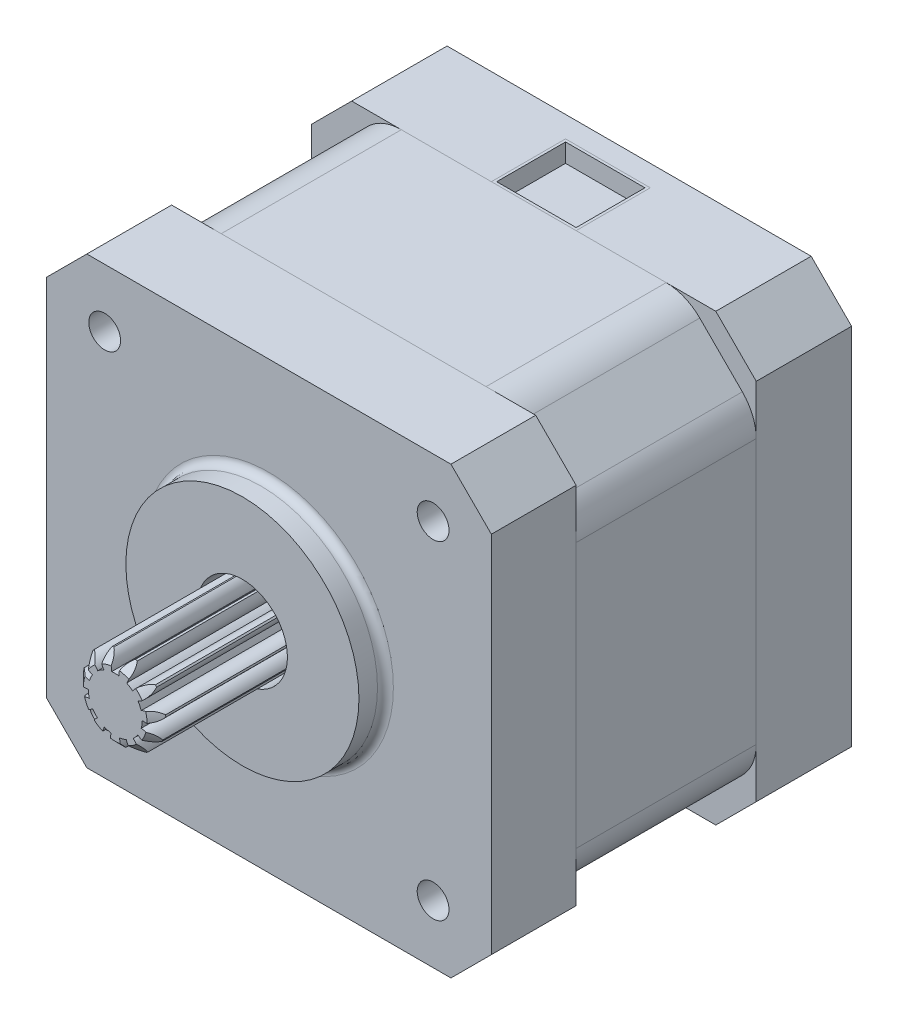
SolidWorks part; units mm, degrees
other "KABLO"
other "ÖN"
other "ORTA"
other "ARKA"
other "ŞAFT"
ref_plane "Front Plane" through (0, 0, 0) normal (0, 0, 1) x (1, 0, 0)
ref_plane "Top Plane" through (0, 0, 0) normal (0, 1, 0) x (1, 0, 0)
ref_plane "Right Plane" through (0, 0, 0) normal (1, 0, 0) x (0, 0, -1)
sketch "Sketch1" plane through (0, 0, 0) normal (0, 0, 1) x (1, 0, 0)
  line L0 (-15.5, 15.5) -> (15.5, 15.5) construction
  line L1 (17.1838, 21) -> (-17.1838, 21)
  line L2 (21, 17.1838) -> (21, -17.1838)
  line L3 (17.1838, -21) -> (-17.1838, -21)
  line L4 (-21, 17.1838) -> (-21, -17.1838)
  line L5 (19.0919, 19.0919) -> (-19.0919, -19.0919) construction
  line L6 (19.0919, -19.0919) -> (-19.0919, 19.0919) construction
  line L7 (15.5, 15.5) -> (15.5, -15.5) construction
  line L8 (15.5, -15.5) -> (-15.5, -15.5) construction
  line L9 (-15.5, -15.5) -> (-15.5, 15.5) construction
  line L10 (17.1838, 21) -> (21, 17.1838)
  line L11 (21, 17.1838) -> (21, 21) construction
  line L12 (21, 21) -> (17.1838, 21) construction
  line L13 (19.0919, 19.0919) -> (21, 21) construction
  line L14 (19.0919, 19.0919) -> (-19.0919, 19.0919) construction
  line L15 (-19.0919, 19.0919) -> (-19.0919, -19.0919) construction
  line L16 (-19.0919, -19.0919) -> (19.0919, -19.0919) construction
  line L17 (19.0919, -19.0919) -> (19.0919, 19.0919) construction
  line L18 (21, -17.1838) -> (17.1838, -21)
  line L19 (-17.1838, -21) -> (-21, -17.1838)
  line L20 (-21, 17.1838) -> (-17.1838, 21)
  line L21 (-19.0919, -19.0919) -> (-21, -21) construction
  line L22 (19.0919, -19.0919) -> (21, -21) construction
  line L23 (-19.0919, 19.0919) -> (-21, 21) construction
  line L24 (21, -17.1838) -> (21, -21) construction
  line L25 (21, -21) -> (17.1838, -21) construction
  line L26 (-17.1838, -21) -> (-21, -21) construction
  line L27 (-21, -21) -> (-21, -17.1838) construction
  line L28 (-21, 17.1838) -> (-21, 21) construction
  line L29 (-21, 21) -> (-17.1838, 21) construction
  circle A0 centre (-15.5, 15.5) radius 1.5 construction
  circle A1 centre (15.5, 15.5) radius 1.5 construction
  circle A2 centre (-15.5, -15.5) radius 1.5 construction
  circle A3 centre (15.5, -15.5) radius 1.5 construction
  point P0 (0, 0)
  dimension "D2" = 3
  dimension "D1" = 42
  dimension "D3" = 31
  dimension "D4" = 54
extrude "Boss-Extrude1" add sketch "Sketch1" against normal blind 8
sketch "Sketch3" plane through (0, 0, -8) normal (0, 0, -1) x (-1, 0, 0)
  line L0 (-19.6881, 15.6673) -> (-15.6673, 19.6881)
  line L1 (15.6673, 19.6881) -> (19.6881, 15.6673)
  line L2 (19.6881, -15.6673) -> (15.6673, -19.6881)
  line L3 (-15.6673, -19.6881) -> (-19.6881, -15.6673)
  line L4 (0, 0) -> (-17.6777, -17.6777) construction
  line L5 (0, 0) -> (17.6777, 17.6777) construction
  line L6 (-17.6777, 17.6777) -> (0, 0) construction
  line L7 (0, 0) -> (17.6777, -17.6777) construction
  line L8 (-17.1838, 21) -> (-21, 17.1838)
  line L9 (-21, 17.1838) -> (-21, -17.1838)
  line L10 (-21, -17.1838) -> (-17.1838, -21)
  line L11 (-17.1838, -21) -> (17.1838, -21)
  line L12 (17.1838, -21) -> (21, -17.1838)
  line L13 (21, -17.1838) -> (21, 17.1838)
  line L14 (21, 17.1838) -> (17.1838, 21)
  line L15 (17.1838, 21) -> (-17.1838, 21)
  line L16 (-17.6777, -17.6777) -> (-19.0919, -19.0919) construction
  line L17 (-21, 12.5) -> (-21, -12.5)
  line L18 (-17.1838, -21) -> (-21, -17.1838) construction
  line L19 (-12.5, -21) -> (12.5, -21)
  line L21 (21, -12.5) -> (21, 12.5)
  line L23 (12.5, 21) -> (-12.5, 21)
  arc A0 (-19.6881, -15.6673) -> (-21, -12.5) centre (-16.5208, -12.5) cw
  arc A1 (-15.6673, -19.6881) -> (-12.5, -21) centre (-12.5, -16.5208) ccw
  arc A2 (15.6673, -19.6881) -> (12.5, -21) centre (12.5, -16.5208) cw
  arc A3 (19.6881, -15.6673) -> (21, -12.5) centre (16.5208, -12.5) ccw
  arc A4 (19.6881, 15.6673) -> (21, 12.5) centre (16.5208, 12.5) cw
  arc A5 (15.6673, 19.6881) -> (12.5, 21) centre (12.5, 16.5208) ccw
  arc A6 (-15.6673, 19.6881) -> (-12.5, 21) centre (-12.5, 16.5208) cw
  arc A7 (-19.6881, 15.6673) -> (-21, 12.5) centre (-16.5208, 12.5) ccw
  dimension "D3" = 25
  dimension "D2" = 50
  dimension "D1" = 0
extrude "Boss-Extrude2" add sketch "Sketch3" along normal blind 17 separate body
sketch "Sketch4" plane through (0, 0, -25) normal (0, 0, -1) x (-1, 0, 0)
  line L8 (-17.1838, 21) -> (-21, 17.1838)
  line L9 (-21, 17.1838) -> (-21, -17.1838)
  line L10 (-21, -17.1838) -> (-17.1838, -21)
  line L11 (-17.1838, -21) -> (17.1838, -21)
  line L12 (17.1838, -21) -> (21, -17.1838)
  line L13 (21, -17.1838) -> (21, 17.1838)
  line L14 (21, 17.1838) -> (17.1838, 21)
  line L15 (17.1838, 21) -> (-17.1838, 21)
  line L16 (-17.1838, 21) -> (-21, 17.1838)
  line L17 (-21, 17.1838) -> (-21, -17.1838)
  line L18 (-21, -17.1838) -> (-17.1838, -21)
  line L19 (-17.1838, -21) -> (17.1838, -21)
  line L20 (17.1838, -21) -> (21, -17.1838)
  line L21 (21, -17.1838) -> (21, 17.1838)
  line L22 (21, 17.1838) -> (17.1838, 21)
  line L23 (17.1838, 21) -> (-17.1838, 21)
  dimension "D1" = 0
extrude "Boss-Extrude3" add sketch "Sketch4" along normal blind 9 separate body
sketch "Sketch5" plane through (0, 0, 0) normal (0, 0, 1) x (1, 0, 0)
  circle A0 centre (-15.5, 15.5) radius 1.5 construction
  circle A1 centre (15.5, 15.5) radius 1.5 construction
  circle A2 centre (15.5, -15.5) radius 1.5 construction
  circle A3 centre (-15.5, -15.5) radius 1.5 construction
  circle A4 centre (-15.5, 15.5) radius 1.5
  circle A5 centre (15.5, 15.5) radius 1.5
  circle A6 centre (15.5, -15.5) radius 1.5
  circle A7 centre (-15.5, -15.5) radius 1.5
extrude "Cut-Extrude1" cut sketch "Sketch5" against normal blind 4.5
sketch "Sketch6" plane through (0, 0, 0) normal (0, 0, 1) x (1, 0, 0)
  circle A0 centre (0, 0) radius 11
  dimension "D1" = 22
extrude "Boss-Extrude4" add sketch "Sketch6" along normal blind 2.5
sketch "Sketch9" plane through (0, 0, 2.5) normal (0, 0, 1) x (1, 0, 0)
  circle A0 centre (0, 0) radius 4.25
  dimension "D1" = 8.5
extrude "Cut-Extrude2" cut sketch "Sketch9" against normal blind 3
sketch "Sketch8" plane through (0, 0, -0.5) normal (0, 0, 1) x (1, 0, 0)
  circle A0 centre (0, 0) radius 3.9
  dimension "D1" = 7.8
extrude "Boss-Extrude5" add sketch "Sketch8" along normal blind 15 separate body
sketch "Sketch11" plane through (0, 0, -0.5) normal (0, 0, 1) x (1, 0, 0)
  circle A2 centre (0, 0) radius 4
  circle A3 centre (0, 0) radius 4.25 construction
  circle A4 centre (0, 0) radius 4.25 construction
  circle A5 centre (0, 0) radius 2.75
  dimension "D2" = 5.5
  dimension "D1" = 0.25
extrude "Boss-Extrude6" add sketch "Sketch11" along normal blind 0.5
fillet "Fillet1" radius 0.75 1 edges at (-11, 0, 0)
sketch "Sketch12" plane through (0, 0, 0) normal (1, 0, 0) x (0, 0, -1)
  line L0 (-14.5, 3) -> (-13.6, 3.9)
  line L1 (-14.5, 3.9) -> (-14.5, -3.9) construction
  line L2 (0.5, 3.9) -> (-14.5, 3.9) construction
  line L3 (-13.6, 3.9) -> (-13.6, 3) construction
  line L4 (-13.6, 3) -> (-14.5, 3) construction
  line L5 (-14.5, 3) -> (-14.5, 3.9)
  line L6 (-14.5, 3.9) -> (-13.6, 3.9)
  line L7 (-14.5, 0) -> (0, 0) construction
  dimension "D1" = 6
revolve "Cut-Revolve1" cut sketch "Sketch12" angle 360 about L7
sketch "Sketch13" plane through (0, 21, 0) normal (0, 1, 0) x (1, 0, 0)
  line L0 (0, 32) -> (0, 25) construction
  line L2 (-12.5, 25) -> (12.5, 25) construction
  line L3 (0, 32) -> (0, 34) construction
  line L4 (-4, 25) -> (4, 25)
  line L5 (-4, 25) -> (-4, 32)
  line L6 (-4, 32) -> (4, 32)
  line L7 (4, 25) -> (4, 32)
  line L8 (-17.1838, 34) -> (17.1838, 34) construction
  dimension "D1" = 2
  dimension "D2" = 8
extrude "Cut-Extrude3" cut sketch "Sketch13" against normal blind 2
sketch "Sketch14" plane through (0, 19, 0) normal (0, 1, 0) x (1, 0, 0)
  line L4 (-4, 32) -> (-4, 25)
  line L5 (-4, 25) -> (4, 25)
  line L6 (4, 25) -> (4, 32)
  line L7 (4, 32) -> (-4, 32)
  line L8 (-4, 32) -> (-4, 25)
  line L9 (-4, 25) -> (4, 25)
  line L10 (4, 25) -> (4, 32)
  line L11 (4, 32) -> (-4, 32)
  dimension "D1" = 0
extrude "Boss-Extrude7" add sketch "Sketch14" along normal blind 0.25 separate body
sketch "Sketch15" plane through (0, 19.25, 0) normal (0, 1, 0) x (1, 0, 0)
  line L0 (3.75, 25.25) -> (3.75, 31.75)
  line L1 (3.75, 31.75) -> (-3.75, 31.75)
  line L2 (-3.75, 31.75) -> (-3.75, 25.25)
  line L3 (-3.75, 25.25) -> (3.75, 25.25)
  line L4 (4, 32) -> (-4, 32)
  line L5 (-4, 32) -> (-4, 25)
  line L6 (-4, 25) -> (4, 25)
  line L7 (4, 25) -> (4, 32)
  line L8 (4, 32) -> (-4, 32)
  line L9 (-4, 32) -> (-4, 25)
  line L10 (-4, 25) -> (4, 25)
  line L11 (4, 25) -> (4, 32)
  dimension "D1" = 0
  dimension "D2" = 0.25
extrude "Boss-Extrude8" add sketch "Sketch15" along normal up to surface (1.75 mm away) up to face at (0, 21, -29)
sketch "Szkic1" plane through (0, 0, 14.5) normal (0, 0, 1) x (1, 0, 0)
  circle A0 centre (0, 0) radius 3.9 construction
  arc A1 (2.1351, -1.3924) -> (3.5094, -1.7012) centre (3.067, -0.4575) ccw
  arc A2 (3.5839, -1.5382) -> (3.872, 0.4662) centre (0, 0) ccw
  arc A3 (3.5839, -1.5382) -> (2.4505, -0.7018) centre (2.3543, -2.0183) ccw
  arc A4 (2.4505, -0.7018) -> (2.5489, -0.017) centre (0, 0) ccw
  arc A5 (2.5489, -0.017) -> (3.872, 0.4662) centre (2.8275, 1.2733) ccw
  arc A6 (3.8465, 0.6436) -> (3.0053, 2.4856) centre (0, 0) ccw
  arc A7 (3.8465, 0.6436) -> (2.4409, 0.7344) centre (3.0717, -0.4251) ccw
  arc A8 (2.4409, 0.7344) -> (2.1535, 1.3638) centre (0, 0) ccw
  arc A9 (2.1535, 1.3638) -> (3.0053, 2.4856) centre (1.6903, 2.5998) ccw
  arc A10 (2.888, 2.621) -> (1.1845, 3.7158) centre (0, 0) ccw
  arc A11 (2.888, 2.621) -> (1.6564, 1.9375) centre (2.8139, 1.3031) ccw
  arc A12 (1.6564, 1.9375) -> (1.0743, 2.3115) centre (0, 0) ccw
  arc A13 (1.0743, 2.3115) -> (1.1845, 3.7158) centre (0.0164, 3.1009) ccw
  arc A14 (2.1833, -3.2316) -> (3.5094, -1.7012) centre (0, 0) ccw
  arc A15 (1.0125, 3.7663) -> (0.3459, 2.5254) centre (1.6627, 2.6175) ccw
  arc A16 (0.3459, 2.5254) -> (-0.3459, 2.5254) centre (0, 0) ccw
  arc A17 (-0.3459, 2.5254) -> (-1.0125, 3.7663) centre (-1.6627, 2.6175) ccw
  arc A18 (-1.1845, 3.7158) -> (-2.888, 2.621) centre (0, 0) ccw
  arc A19 (-1.1845, 3.7158) -> (-1.0743, 2.3115) centre (-0.0164, 3.1009) ccw
  arc A20 (-1.0743, 2.3115) -> (-1.6564, 1.9375) centre (0, 0) ccw
  arc A21 (-1.6564, 1.9375) -> (-2.888, 2.621) centre (-2.8139, 1.3031) ccw
  arc A22 (-3.0053, 2.4856) -> (-3.8465, 0.6436) centre (0, 0) ccw
  arc A23 (-3.0053, 2.4856) -> (-2.1535, 1.3638) centre (-1.6903, 2.5998) ccw
  arc A24 (-2.1535, 1.3638) -> (-2.4409, 0.7344) centre (0, 0) ccw
  arc A25 (-2.4409, 0.7344) -> (-3.8465, 0.6436) centre (-3.0717, -0.4251) ccw
  arc A26 (-3.872, 0.4662) -> (-3.5839, -1.5382) centre (0, 0) ccw
  arc A27 (-3.872, 0.4662) -> (-2.5489, -0.017) centre (-2.8275, 1.2733) ccw
  arc A28 (-2.5489, -0.017) -> (-2.4505, -0.7018) centre (0, 0) ccw
  arc A29 (-2.4505, -0.7018) -> (-3.5839, -1.5382) centre (-2.3543, -2.0183) ccw
  arc A30 (-3.5094, -1.7012) -> (-2.1833, -3.2316) centre (0, 0) ccw
  arc A31 (-3.5094, -1.7012) -> (-2.1351, -1.3924) centre (-3.067, -0.4575) ccw
  arc A32 (-2.1351, -1.3924) -> (-1.6821, -1.9152) centre (0, 0) ccw
  arc A33 (-1.6821, -1.9152) -> (-2.1833, -3.2316) centre (-0.8894, -2.9707) ccw
  arc A34 (-2.0326, -3.3285) -> (-0.0896, -3.899) centre (0, 0) ccw
  arc A35 (-2.0326, -3.3285) -> (-1.0434, -2.3257) centre (-2.3328, -2.0431) ccw
  arc A36 (-1.0434, -2.3257) -> (-0.3796, -2.5206) centre (0, 0) ccw
  arc A37 (-0.3796, -2.5206) -> (-0.0896, -3.899) centre (0.8579, -2.98) ccw
  arc A38 (0.0896, -3.899) -> (2.0326, -3.3285) centre (0, 0) ccw
  arc A39 (0.0896, -3.899) -> (0.3796, -2.5206) centre (-0.8579, -2.98) ccw
  arc A40 (0.3796, -2.5206) -> (1.0434, -2.3257) centre (0, 0) ccw
  arc A41 (1.0434, -2.3257) -> (2.0326, -3.3285) centre (2.3328, -2.0431) ccw
  arc A43 (2.1833, -3.2316) -> (1.6821, -1.9152) centre (0.8894, -2.9707) ccw
  arc A44 (1.6821, -1.9152) -> (2.1351, -1.3924) centre (0, 0) ccw
  arc A45 (1.0125, 3.7663) -> (-1.0125, 3.7663) centre (0, 0) ccw
extrude "Wytnij-wyciągnięcie1" cut sketch "Szkic1" against normal blind 15
sketch "Szkic2" plane through (0, 0, -34) normal (0, 0, -1) x (-1, 0, 0)
  circle A0 centre (0, 0) radius 4.25 construction
  circle A1 centre (0, 0) radius 11 construction
  circle A2 centre (0, 0) radius 4.25
  circle A3 centre (0, 0) radius 11
extrude "Wytnij-wyciągnięcie2" cut sketch "Szkic2" against normal blind 1 contours A3
extrude "Wytnij-wyciągnięcie7" cut sketch "Szkic2<4>" against normal blind 2 contours A2
sketch "Szkic2<4>" plane through (0, 0, -34) normal (0, 0, -1) x (-1, 0, 0) same geometry as "Szkic2"
sketch "Szkic3" plane through (0, 0, -32) normal (0, 0, -1) x (-1, 0, 0)
  circle A0 centre (0, 0) radius 3.5
  circle A1 centre (0, 0) radius 3.6
  dimension "D1" = 0.1
extrude "Wytnij-wyciągnięcie10" cut sketch "Szkic3" against normal blind 5 contours A1 A0 region at (3.5898, 0, -32)
sketch "Szkic4" plane through (0, 0, -32) normal (0, 0, -1) x (-1, 0, 0)
  circle A0 centre (0, 0) radius 0.5
extrude "Wytnij-wyciągnięcie11" cut sketch "Szkic4" against normal blind 3
fillet "Zaokrąglenie1" radius 0.5 1 edges at (-0.5, 0, -29)
chamfer "Sfazowanie1" distance 0.4 angle 45 2 edges at (-0.5, 0, -32) (-3.5, 0, -32)
sketch "Szkic5" plane through (0, 0, -34) normal (0, 0, -1) x (-1, 0, 0)
  circle A0 centre (15.5, -15.5) radius 1.5 construction
  circle A1 centre (15.5, 15.5) radius 1.5 construction
  circle A2 centre (-15.5, 15.5) radius 1.5 construction
  circle A3 centre (-15.5, -15.5) radius 1.5 construction
  circle A4 centre (15.5, -15.5) radius 1.5
  circle A5 centre (15.5, 15.5) radius 1.5
  circle A6 centre (-15.5, 15.5) radius 1.5
  circle A7 centre (-15.5, -15.5) radius 1.5
  circle A8 centre (-15.5, -15.5) radius 3.3
  circle A9 centre (-15.5, 15.5) radius 3.3
  circle A10 centre (15.5, 15.5) radius 3.3
  circle A11 centre (15.5, -15.5) radius 3.3
extrude "Wytnij-wyciągnięcie12" cut sketch "Szkic5" against normal blind 3 contours A8 | A9 | A10 | A11
extrude "Wytnij-wyciągnięcie13" cut sketch "Szkic5<3>" against normal blind 15 contours A4 | A5 | A6 | A7 region at (-15.5, -15.5, -34) region at (-15.5, 15.5, -34) region at (15.5, 15.5, -34) region at (15.5, -15.5, -34)
sketch "Szkic5<3>" plane through (0, 0, -34) normal (0, 0, -1) x (-1, 0, 0) same geometry as "Szkic5"
